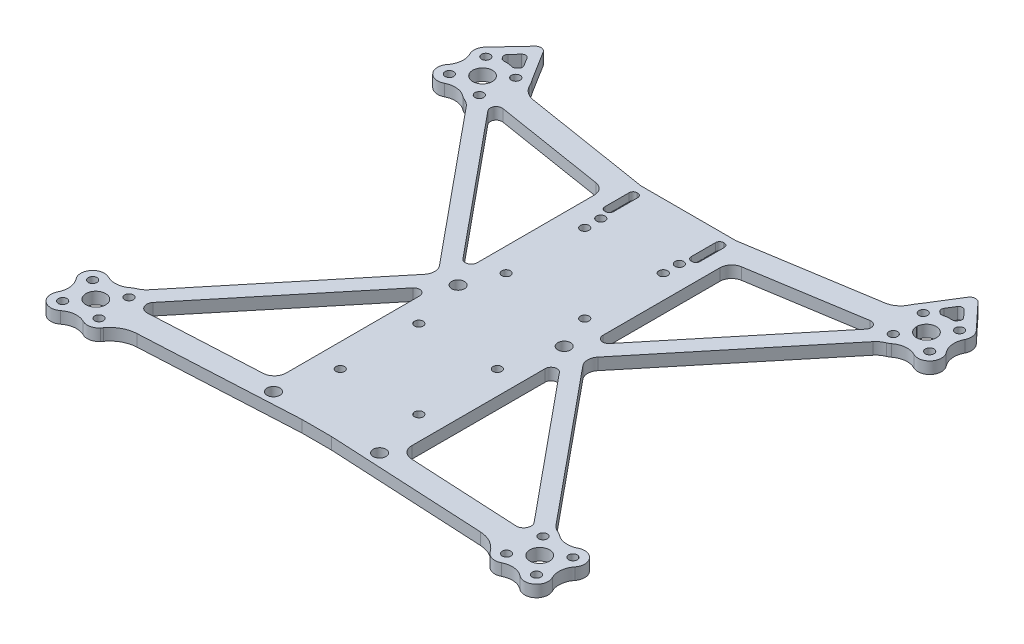
SolidWorks part; units mm, degrees
ref_plane "Front Plane" through (0, 0, 0) normal (0, 0, 1) x (1, 0, 0)
ref_plane "Top Plane" through (0, 0, 0) normal (0, 1, 0) x (1, 0, 0)
ref_plane "Right Plane" through (0, 0, 0) normal (1, 0, 0) x (0, 0, -1)
sketch "Sketch1" plane through (0, 0, 0) normal (0, 1, 0) x (1, 0, 0)
  line L0 (0, 42.225) -> (0, -42.225) construction
  line L1 (16, 42.225) -> (-16, 42.225)
  line L2 (16, 42.225) -> (16, -42.225)
  line L3 (16, -42.225) -> (-16, -42.225)
  line L4 (-16, 42.225) -> (-16, -42.225)
  line L5 (16, 42.225) -> (-16, -42.225) construction
  line L6 (16, -42.225) -> (-16, 42.225) construction
  line L12 (-12.1, 50.425) -> (-12.1, 52.425) construction
  line L13 (-7.9, 52.425) -> (7.9, 52.425)
  line L17 (-11, 52.425) -> (-11, 42.225) construction
  line L18 (-7.9, 42.225) -> (-14.1, 42.225)
  line L20 (-10, 36) -> (10, 36)
  line L21 (-10, 36) -> (-10, 16)
  line L22 (-10, 16) -> (10, 16)
  line L23 (10, 36) -> (10, 16)
  line L24 (-10, 36) -> (10, 16) construction
  line L25 (-10, 16) -> (10, 36) construction
  line L26 (-14.5, 10.775) -> (14.5, 10.775)
  line L27 (-14.5, 10.775) -> (-14.5, 41.225)
  line L28 (-14.5, 41.225) -> (14.5, 41.225)
  line L29 (14.5, 10.775) -> (14.5, 41.225)
  line L30 (-14.5, 10.775) -> (14.5, 41.225) construction
  line L31 (-14.5, 41.225) -> (14.5, 10.775) construction
  line L32 (-10, -6.225) -> (10, -6.225)
  line L33 (-10, -6.225) -> (-10, -26.225)
  line L34 (-10, -26.225) -> (10, -26.225)
  line L35 (10, -6.225) -> (10, -26.225)
  line L36 (-10, -6.225) -> (10, -26.225) construction
  line L37 (-10, -26.225) -> (10, -6.225) construction
  line L38 (-15.75, -36.225) -> (15.75, -36.225)
  line L39 (-15.75, -36.225) -> (-15.75, 3.775)
  line L40 (-15.75, 3.775) -> (15.75, 3.775)
  line L41 (15.75, -36.225) -> (15.75, 3.775)
  line L42 (-15.75, -36.225) -> (15.75, 3.775) construction
  line L43 (-15.75, 3.775) -> (15.75, -36.225) construction
  line L48 (-7.9, 42.225) -> (-7.9, 52.425)
  line L49 (-7.9, 52.425) -> (-14.1, 52.425)
  line L59 (-14.1, 42.225) -> (-14.1, 52.425)
  line L63 (-12.1, 50.425) -> (-9.9, 50.425)
  line L64 (-12.1, 50.425) -> (-12.1, 42.225)
  line L65 (-12.1, 42.225) -> (-9.9, 42.225)
  line L66 (-9.9, 50.425) -> (-9.9, 42.225)
  line L67 (-12.1, 50.425) -> (-9.9, 42.225) construction
  line L68 (-12.1, 42.225) -> (-9.9, 50.425) construction
  line L69 (-12.1, 50.425) -> (-14.1, 50.425) construction
  line L74 (7.9, 42.225) -> (14.1, 42.225)
  line L75 (14.1, 42.225) -> (14.1, 52.425)
  line L76 (7.9, 52.425) -> (14.1, 52.425)
  line L77 (7.9, 42.225) -> (7.9, 52.425)
  line L78 (12.1, 50.425) -> (9.9, 50.425)
  line L79 (12.1, 50.425) -> (12.1, 42.225)
  line L80 (12.1, 42.225) -> (9.9, 42.225)
  line L81 (9.9, 50.425) -> (9.9, 42.225)
  line L82 (-14.5, 10.775) -> (-14.5, 3.775) construction
  line L83 (-14.5, 7.275) -> (16, 7.275) construction
  line L89 (-13.5, -37.225) -> (-16, -37.225) construction
  line L94 (-14.1, 52.425) -> (-16, 52.425)
  line L95 (-14.1, 52.425) -> (-14.1, 42.225)
  line L96 (-14.1, 42.225) -> (-16, 42.225)
  line L97 (-16, 52.425) -> (-16, 42.225)
  line L98 (14.1, 52.425) -> (16, 52.425)
  line L99 (14.1, 52.425) -> (14.1, 42.225)
  line L100 (14.1, 42.225) -> (16, 42.225)
  line L101 (16, 52.425) -> (16, 42.225)
  circle A3 centre (-10, 36) radius 1.1
  circle A4 centre (10, 36) radius 1.1
  circle A5 centre (10, 16) radius 1.1
  circle A6 centre (-10, 16) radius 1.1
  circle A7 centre (-10, -6.225) radius 1.1
  circle A8 centre (10, -6.225) radius 1.1
  circle A9 centre (10, -26.225) radius 1.1
  circle A10 centre (-10, -26.225) radius 1.1
  circle A37 centre (-13.5, 7.275) radius 2.5
  circle A38 centre (-13.5, 7.275) radius 1.625
  circle A39 centre (13.5, 7.275) radius 1.625
  circle A40 centre (-13.5, -39.725) radius 2.5
  circle A41 centre (-13.5, -39.725) radius 1.625
  circle A42 centre (13.5, -39.725) radius 1.625
  circle A43 centre (-11, 46.325) radius 1.1
  circle A44 centre (11, 46.325) radius 1.1
  point P0 (0, 0)
  point P8 (0, 0)
  point P16 (0, 26)
  point P26 (0, 26)
  point P31 (0, -16.225)
  point P36 (0, -16.225)
  point P61 (-11, 46.325)
  dimension "D3" = 2
  dimension "D17" = 2.2
  dimension "D22" = 5
  dimension "D23" = 3.25
  dimension "D8" = 32
  dimension "D9" = 22
  dimension "D10" = 20
  dimension "D11" = 29
  dimension "D12" = 30.45
  dimension "D13" = 40
  dimension "D14" = 31.5
  dimension "D15" = 1
  dimension "D16" = 7
  dimension "D18" = 2.2
  dimension "D20" = 8.2
  dimension "D24" = 1
extrude "Base shape" add sketch "Sketch1" along normal blind 2 contours L63 L66 L1 L48 L49 L59 L18 L64 | L81 L78 L79 L1 L75 L76 L77 | L94 L97 L1 L59 | L101 L98 L75 L1 | L1 L77 L13 L48 | A43 L66 L63 L64 | A43 L64 L18 L66 | L79 A44 L81 L74 | L81 A44 L79 L78 | L1 L4 L3 L2 | A4 | A3 | A7 | A8 | A9 | A10 | A5 | A6 | A39 | A38 | A41 | A42 region at (15.05, 0, -47.325) region at (13.1, 0, -42.3444) region at (11, 0, -43.8523) region at (11, 0, -48.7977) region at (0, 0, -47.325) region at (-8.0194, 0, -47.325) region at (-15.05, 0, -47.325) region at (-11, 0, -43.8523) region at (-11, 0, -48.7977)
sketch "Sketch2" plane through (0, 2, 0) normal (0, -1, 0) x (1, 0, 0)
  line L0 (0, -52.425) -> (0, 42.225) construction
  line L1 (11.1, -42.225) -> (10.9, -42.225)
  line L2 (12.1, -43.225) -> (12.1, -49.425)
  line L3 (11.1, -50.425) -> (10.9, -50.425)
  line L4 (9.9, -43.225) -> (9.9, -49.425)
  line L5 (12.1, -42.225) -> (9.9, -50.425) construction
  line L6 (12.1, -50.425) -> (9.9, -42.225) construction
  line L7 (16, -52.425) -> (-16, -52.425) construction
  line L12 (16, 42.225) -> (-16, 42.225) construction
  line L13 (-11.1, -42.225) -> (-10.9, -42.225)
  line L14 (-12.1, -43.225) -> (-12.1, -49.425)
  line L15 (-11.1, -50.425) -> (-10.9, -50.425)
  line L20 (-9.9, -43.225) -> (-9.9, -49.425)
  arc A2 (12.1, -49.425) -> (11.1, -50.425) centre (11.1, -49.425) cw
  arc A3 (10.9, -50.425) -> (9.9, -49.425) centre (10.9, -49.425) cw
  arc A4 (10.9, -42.225) -> (9.9, -43.225) centre (10.9, -43.225) ccw
  arc A5 (11.1, -42.225) -> (12.1, -43.225) centre (11.1, -43.225) cw
  arc A6 (-10.9, -42.225) -> (-9.9, -43.225) centre (-10.9, -43.225) cw
  arc A7 (-11.1, -42.225) -> (-12.1, -43.225) centre (-11.1, -43.225) ccw
  arc A8 (-12.1, -49.425) -> (-11.1, -50.425) centre (-11.1, -49.425) ccw
  arc A9 (-10.9, -50.425) -> (-9.9, -49.425) centre (-10.9, -49.425) ccw
  point P0 (11, -46.325)
  dimension "D3" = 1
  dimension "D1" = 8.2
  dimension "D2" = 2.2
extrude "Cut-Extrude2" cut sketch "Sketch2" along normal blind 1
fillet "Main fillets" radius 2.5 4 edges at (-16, 1, -52.425) (16, 1, -52.425) (-16, 1, 42.225) (16, 1, 42.225)
sketch "Sketch3" plane through (0, 2, 0) normal (0, 1, 0) x (1, 0, 0)
  line L0 (-11.1, 50.425) -> (-10.9, 50.425) construction
  line L1 (-9.9, 49.425) -> (-9.9, 43.225) construction
  line L2 (-10.9, 42.225) -> (-11.1, 42.225) construction
  line L3 (-12.1, 43.225) -> (-12.1, 49.425) construction
  line L4 (-11.1, 50.425) -> (-10.9, 50.425)
  line L5 (-9.9, 49.425) -> (-9.9, 43.225)
  line L6 (-10.9, 42.225) -> (-11.1, 42.225)
  line L7 (-12.1, 43.225) -> (-12.1, 49.425)
  line L8 (13.5, 52.425) -> (-13.5, 52.425)
  line L9 (-16, 49.925) -> (-16, -39.725)
  line L10 (-13.5, -42.225) -> (13.5, -42.225)
  line L11 (16, -39.725) -> (16, 49.925)
  line L12 (10.9, 50.425) -> (11.1, 50.425) construction
  line L13 (12.1, 49.425) -> (12.1, 43.225) construction
  line L14 (11.1, 42.225) -> (10.9, 42.225) construction
  line L15 (9.9, 43.225) -> (9.9, 49.425) construction
  line L16 (13.5, 52.425) -> (-13.5, 52.425)
  line L17 (-16, 49.925) -> (-16, -39.725)
  line L18 (-13.5, -42.225) -> (13.5, -42.225)
  line L19 (16, -39.725) -> (16, 49.925)
  line L24 (10.9, 50.425) -> (11.1, 50.425)
  line L25 (12.1, 49.425) -> (12.1, 43.225)
  line L30 (11.1, 42.225) -> (10.9, 42.225)
  line L31 (9.9, 43.225) -> (9.9, 49.425)
  circle A0 centre (13.5, -39.725) radius 1.625 construction
  circle A1 centre (-13.5, -39.725) radius 1.625 construction
  circle A2 centre (-13.5, 7.275) radius 1.625 construction
  circle A3 centre (-10, -6.225) radius 1.1 construction
  circle A4 centre (-10, -26.225) radius 1.1 construction
  circle A5 centre (10, -26.225) radius 1.1 construction
  circle A6 centre (10, -6.225) radius 1.1 construction
  circle A7 centre (13.5, 7.275) radius 1.625 construction
  arc A8 (-13.5, 52.425) -> (-16, 49.925) centre (-13.5, 49.925) ccw
  arc A9 (-16, -39.725) -> (-13.5, -42.225) centre (-13.5, -39.725) ccw
  arc A10 (13.5, -42.225) -> (16, -39.725) centre (13.5, -39.725) ccw
  arc A11 (16, 49.925) -> (13.5, 52.425) centre (13.5, 49.925) ccw
  arc A13 (-11.1, 50.425) -> (-12.1, 49.425) centre (-11.1, 49.425) ccw construction
  arc A14 (-9.9, 49.425) -> (-10.9, 50.425) centre (-10.9, 49.425) ccw construction
  arc A16 (-13.5, 52.425) -> (-16, 49.925) centre (-13.5, 49.925) ccw
  arc A17 (-16, -39.725) -> (-13.5, -42.225) centre (-13.5, -39.725) ccw
  arc A18 (13.5, -42.225) -> (16, -39.725) centre (13.5, -39.725) ccw
  arc A19 (16, 49.925) -> (13.5, 52.425) centre (13.5, 49.925) ccw
  circle A24 centre (-10, 16) radius 1.1 construction
  circle A25 centre (-10, 36) radius 1.1 construction
  circle A26 centre (10, 36) radius 1.1 construction
  circle A27 centre (10, 16) radius 1.1 construction
  circle A28 centre (10, 16) radius 1.1
  circle A29 centre (10, 36) radius 1.1
  circle A30 centre (-10, 36) radius 1.1
  circle A31 centre (-10, 16) radius 1.1
  circle A32 centre (13.5, 7.275) radius 1.625
  circle A33 centre (10, -6.225) radius 1.1
  circle A34 centre (10, -26.225) radius 1.1
  circle A35 centre (-10, -26.225) radius 1.1
  circle A36 centre (-10, -6.225) radius 1.1
  circle A37 centre (13.5, -39.725) radius 1.625
  circle A38 centre (-13.5, -39.725) radius 1.625
  circle A39 centre (-13.5, 7.275) radius 1.625
  arc A40 (-10.9, 42.225) -> (-9.9, 43.225) centre (-10.9, 43.225) ccw construction
  arc A41 (-12.1, 43.225) -> (-11.1, 42.225) centre (-11.1, 43.225) ccw construction
  arc A42 (-11.1, 50.425) -> (-12.1, 49.425) centre (-11.1, 49.425) ccw
  arc A43 (-9.9, 49.425) -> (-10.9, 50.425) centre (-10.9, 49.425) ccw
  arc A44 (-10.9, 42.225) -> (-9.9, 43.225) centre (-10.9, 43.225) ccw
  arc A45 (-12.1, 43.225) -> (-11.1, 42.225) centre (-11.1, 43.225) ccw
  arc A46 (10.9, 50.425) -> (9.9, 49.425) centre (10.9, 49.425) ccw construction
  arc A47 (12.1, 49.425) -> (11.1, 50.425) centre (11.1, 49.425) ccw construction
  arc A48 (11.1, 42.225) -> (12.1, 43.225) centre (11.1, 43.225) ccw construction
  arc A49 (9.9, 43.225) -> (10.9, 42.225) centre (10.9, 43.225) ccw construction
  arc A50 (10.9, 50.425) -> (9.9, 49.425) centre (10.9, 49.425) ccw
  arc A51 (12.1, 49.425) -> (11.1, 50.425) centre (11.1, 49.425) ccw
  arc A52 (11.1, 42.225) -> (12.1, 43.225) centre (11.1, 43.225) ccw
  arc A53 (9.9, 43.225) -> (10.9, 42.225) centre (10.9, 43.225) ccw
  dimension "D1" = 0
extrude "Thicker base" add sketch "Sketch3" along normal blind 1
sketch "Sketch4" plane through (0, 0, 0) normal (0, -1, 0) x (1, 0, 0)
  line L0 (0, 13.9568) -> (0, -8.6953) construction
  line L1 (-13.1, -38.5) -> (-6.9, -38.5)
  line L2 (-14.1, -39.5) -> (-14.1, -40.7)
  line L3 (-13.1, -41.7) -> (-6.9, -41.7)
  line L4 (-5.9, -39.5) -> (-5.9, -40.7)
  line L5 (-10, -38.5) -> (-10, -41.7) construction
  line L7 (13.1, -38.5) -> (6.9, -38.5)
  line L8 (14.1, -39.5) -> (14.1, -40.7)
  line L9 (13.1, -41.7) -> (6.9, -41.7)
  line L10 (5.9, -39.5) -> (5.9, -40.7)
  line L12 (-14.1, -40.1) -> (-5.9, -40.1) construction
  circle A0 centre (-10, -36) radius 2
  arc A9 (14.1, -40.7) -> (13.1, -41.7) centre (13.1, -40.7) cw
  arc A10 (13.1, -38.5) -> (14.1, -39.5) centre (13.1, -39.5) cw
  arc A11 (6.9, -41.7) -> (5.9, -40.7) centre (6.9, -40.7) cw
  arc A12 (6.9, -38.5) -> (5.9, -39.5) centre (6.9, -39.5) ccw
  arc A13 (-6.9, -41.7) -> (-5.9, -40.7) centre (-6.9, -40.7) ccw
  arc A14 (-6.9, -38.5) -> (-5.9, -39.5) centre (-6.9, -39.5) cw
  arc A15 (-14.1, -40.7) -> (-13.1, -41.7) centre (-13.1, -40.7) ccw
  arc A16 (-13.1, -38.5) -> (-14.1, -39.5) centre (-13.1, -39.5) ccw
  point P9 (-10, -38)
  point P19 (14.1, -41.7)
  point P24 (14.1, -38.5)
  point P27 (5.9, -41.7)
  point P30 (5.9, -38.5)
  point P33 (-5.9, -41.7)
  point P36 (-5.9, -38.5)
  point P39 (-14.1, -41.7)
  point P42 (-14.1, -38.5)
  dimension "D5" = 4
  dimension "D6" = 1
  dimension "D1" = 8.2
  dimension "D2" = 3.2
  dimension "D3" = 10
  dimension "D4" = 0.5
extrude "Battery holder pockets" cut sketch "Sketch4" against normal blind 1 contours L4 L1 L2 L3 | L7 L10 L9 L8 region at (-10, 0, -40.1) region at (10, 0, -40.1)
sketch "Sketch5" plane through (0, 1, 0) normal (0, -1, 0) x (1, 0, 0)
  line L0 (-10, -38.5) -> (-10, -41.7) construction
  line L2 (-13.1, -41.7) -> (-6.9, -41.7) construction
  line L3 (0, 5.9884) -> (0, -5.6723) construction
  line L4 (-13.1, -38.5) -> (-6.9, -38.5) construction
  circle A0 centre (-10, -40.1) radius 1.1
  circle A1 centre (10, -40.1) radius 1.1
  dimension "D1" = 2.2
extrude "Battery holder holes" cut sketch "Sketch5" against normal up to next
sketch "Sketch6" [suppressed] plane through (0, 0, 0) normal (0, -1, 0) x (1, 0, 0)
  line L0 (0, -5.1) -> (0, 9.653) construction
  line L8 (-13.5, -7.275) -> (13.5, -7.275) construction
  line L10 (-16, -25.775) -> (16, -25.775) construction
  line L11 (-16, -49.925) -> (-16, 39.725) construction
  line L12 (16, -49.925) -> (16, 39.725) construction
  line L13 (17.5, -34.275) -> (19, -34.275)
  line L14 (16, -37.275) -> (19, -37.275)
  line L15 (16, -37.275) -> (16, -14.275)
  line L16 (16, -14.275) -> (19, -14.275)
  line L17 (19, -37.275) -> (19, -14.275)
  line L18 (16, -37.275) -> (19, -14.275) construction
  line L19 (16, -14.275) -> (19, -37.275) construction
  line L20 (16, -35.775) -> (17.5, -35.775)
  line L21 (16, -35.775) -> (16, -15.775)
  line L22 (16, -15.775) -> (17.5, -15.775)
  line L23 (17.5, -35.775) -> (17.5, -15.775)
  line L24 (16, -35.775) -> (17.5, -15.775) construction
  line L25 (16, -15.775) -> (17.5, -35.775) construction
  line L26 (17.5, -17.275) -> (19, -17.275)
  line L27 (-17.5, -34.275) -> (-19, -34.275)
  line L28 (-17.5, -17.275) -> (-19, -17.275)
  line L29 (-16, -35.775) -> (-16, -15.775)
  line L30 (-16, -35.775) -> (-17.5, -35.775)
  line L31 (-17.5, -35.775) -> (-17.5, -15.775)
  line L32 (-16, -15.775) -> (-17.5, -15.775)
  line L33 (-16, -37.275) -> (-16, -14.275)
  line L34 (-16, -37.275) -> (-19, -37.275)
  line L35 (-19, -37.275) -> (-19, -14.275)
  line L36 (-16, -14.275) -> (-19, -14.275)
  line L37 (16, 22.725) -> (19, 22.725)
  line L38 (16, 22.725) -> (16, -0.275)
  line L39 (16, -0.275) -> (19, -0.275)
  line L40 (19, 22.725) -> (19, -0.275)
  line L41 (16, 21.225) -> (17.5, 21.225)
  line L42 (16, 21.225) -> (16, 1.225)
  line L43 (16, 1.225) -> (17.5, 1.225)
  line L44 (17.5, 21.225) -> (17.5, 1.225)
  line L45 (17.5, 2.725) -> (19, 2.725)
  line L46 (17.5, 19.725) -> (19, 19.725)
  line L47 (-17.5, 19.725) -> (-19, 19.725)
  line L48 (-17.5, 2.725) -> (-19, 2.725)
  line L49 (-16, 21.225) -> (-16, 1.225)
  line L50 (-16, 21.225) -> (-17.5, 21.225)
  line L51 (-17.5, 21.225) -> (-17.5, 1.225)
  line L52 (-16, 1.225) -> (-17.5, 1.225)
  line L53 (-16, 22.725) -> (-16, -0.275)
  line L54 (-16, 22.725) -> (-19, 22.725)
  line L55 (-19, 22.725) -> (-19, -0.275)
  line L56 (-16, -0.275) -> (-19, -0.275)
  point P19 (17.5, -25.775)
  point P25 (16.75, -25.775)
  line M18 (16, -49.925) -> (16, 39.725)
  line M22 (-16, 39.725) -> (-16, -49.925)
  dimension "D1" = 14
  dimension "D4" = 23
  dimension "D5" = 3
  dimension "D6" = 1.5
  dimension "D7" = 20
  dimension "D8" = 1.5
extrude "Strap holders" [suppressed] add sketch "Sketch6" against normal up to surface (2 mm away) contours L23 L20 L14 L17 L13 M18 | L23 L26 L17 L16 L22 M18 | L45 L44 L43 L39 L40 M18 | L44 L46 L40 L37 L38 L41 | L54 L55 L47 L51 L50 M22 | L56 L52 L51 L48 L55 M22 | L36 L35 L28 L31 L32 M22 | L35 L34 L30 L31 L27 M22 up to face at (-10, 3, -39)
fillet "Strap holder fillets" [suppressed] radius 0.75
sketch "Sketch7" plane through (0, 3, 0) normal (0, 1, 0) x (1, 0, 0)
  line L0 (-56.5, 56.5) -> (-16, 50.0116) construction
  line L1 (56.5, -56.5) -> (-56.5, -56.5)
  line L2 (56.5, -56.5) -> (56.5, 56.5)
  line L3 (56.5, 56.5) -> (-56.5, 56.5)
  line L4 (-56.5, -56.5) -> (-56.5, 56.5)
  line L5 (56.5, -56.5) -> (-56.5, 56.5) construction
  line L6 (56.5, 56.5) -> (-56.5, -56.5) construction
  line L7 (-16, 49.925) -> (-16, -39.725) construction
  line L8 (-56.9746, 53.5378) -> (-16.4746, 47.0493)
  line L9 (-47.647, 58.1199) -> (-12.1, 52.425)
  line L10 (-56.0254, 59.4622) -> (-15.5254, 52.9738) construction
  line L11 (-13.5, 7.275) -> (13.5, 7.275) construction
  line L12 (-63.45, 50.7819) -> (-49.55, 62.2181) construction
  line L13 (-56.5, 56.5) -> (-16, 7.275) construction
  line L14 (-58.0444, 55.2293) -> (-17.5444, 6.0043)
  line L15 (-54.9556, 57.7707) -> (-14.4556, 8.5457)
  line L16 (-17.5444, 6.0043) -> (-16, 4.1271)
  line L17 (-56.5, 56.5) -> (-60.3121, 61.1333) construction
  line L18 (-56.5, 65.5) -> (-56.5, 47.5) construction
  line L19 (-60.3121, 61.1333) -> (-51.8667, 60.3121) construction
  line L20 (-56.0894, 60.7227) -> (-55.3151, 68.6852) construction
  line L21 (-56.4116, 69.7087) -> (-62.3842, 63.31)
  line L22 (-54.0419, 69.4782) -> (-49.414, 62.0488)
  line L23 (-55.4603, 67.1922) -> (-58.7341, 63.6848)
  line L24 (-55.4603, 67.1922) -> (-52.9235, 63.1198)
  line L25 (-58.0444, -40.6793) -> (-17.5444, 8.5457)
  line L26 (-54.9556, -43.2207) -> (-14.4556, 6.0043)
  line L27 (-56.5, -41.95) -> (-13.5, -39.725) construction
  line L28 (-47.871, -44.5075) -> (-3.7595, -42.225)
  line L29 (-56.655, -38.954) -> (-16, -36.8503)
  line L30 (-56.345, -44.946) -> (-14.5762, -42.7847) construction
  line L31 (-56.5, -41.95) -> (-14.7312, -39.7887) construction
  line L32 (-13.5, -42.225) -> (13.5, -42.225) construction
  line L33 (-56.655, -38.954) -> (-14.8862, -36.7927) construction
  line L34 (-16.4746, 47.0493) -> (-16, 46.9733)
  line L35 (-12.1, 49.425) -> (-12.1, 52.425) construction
  line L36 (13.5, 52.425) -> (-13.5, 52.425) construction
  circle A0 centre (-56.5, 56.5) radius 38.1
  circle A1 centre (-56.5, 56.5) radius 9
  circle A2 centre (-56.5, 56.5) radius 6
  circle A3 centre (-51.8667, 60.3121) radius 1.1
  circle A4 centre (-61.1333, 52.6879) radius 1.1
  circle A5 centre (-60.3121, 61.1333) radius 1.1
  circle A6 centre (-52.6879, 51.8667) radius 1.1
  circle A7 centre (-60.3121, 61.1333) radius 3
  circle A8 centre (-51.8667, 60.3121) radius 3
  circle A9 centre (-61.1333, 52.6879) radius 3
  circle A10 centre (-52.6879, 51.8667) radius 3
  circle A12 centre (-56.5, 56.5) radius 2.5
  circle A13 centre (-55.3151, 68.6852) radius 1.5
  circle A14 centre (-67.313, 57.5515) radius 4.864
  circle A15 centre (-57.5515, 45.687) radius 4.864
  circle A16 centre (-43.9819, 62.4587) radius 4.864
  circle A17 centre (-55.5501, 44.5421) radius 4.864
  circle A18 centre (-46.9606, 50.4143) radius 1.5
  circle A20 centre (-56.5, -41.95) radius 6
  circle A21 centre (-52.6879, -37.3167) radius 1.1
  circle A22 centre (-61.1333, -38.1379) radius 1.1
  circle A23 centre (-60.3121, -46.5833) radius 1.1
  circle A24 centre (-51.8667, -45.7621) radius 1.1
  circle A25 centre (-51.8667, -45.7621) radius 3
  circle A26 centre (-52.6879, -37.3167) radius 3
  circle A27 centre (-56.5, -41.95) radius 2.5
  circle A28 centre (-60.3121, -46.5833) radius 3
  circle A29 centre (-67.313, -43.0015) radius 4.864
  circle A30 centre (-61.1333, -38.1379) radius 3
  circle A31 centre (-57.5515, -31.137) radius 4.864
  circle A32 centre (-55.5501, -29.9921) radius 4.864
  circle A34 centre (-56.5, -41.95) radius 9
  circle A35 centre (-55.4485, -52.763) radius 4.864
  circle A38 centre (-43.36, -51.5674) radius 7.2836
  circle A39 centre (-47.0369, -36.5665) radius 1.8873
  point P0 (0, 0)
  point P15 (0, 0)
  point P36 (-52.6879, 51.8667)
  point P54 (-55.4603, 67.1922)
  point P111 (-12.1, 49.425)
  line M22 (13.5, 52.425) -> (-13.5, 52.425)
  arc M23 (-13.5, 52.425) -> (-16, 49.925) centre (-13.5, 49.925) ccw
  line M24 (-16, 49.925) -> (-16, -39.725)
  arc M25 (-16, -39.725) -> (-13.5, -42.225) centre (-13.5, -39.725) ccw
  line M26 (-13.5, -42.225) -> (13.5, -42.225)
  dimension "D3" = 76.2
  dimension "D4" = 12
  dimension "D5" = 3
  dimension "D10" = 2.2
  dimension "D11" = 5
  dimension "D12" = 3
  dimension "D16" = 3
  dimension "D1" = 113
  dimension "D13" = 8
  dimension "D6" = 3
  dimension "D7" = 3
  dimension "D8" = 2
  dimension "D9" = 2
  dimension "D14" = 3
  dimension "D15" = 3
extrude "Arms" add sketch "Sketch7" against normal up to surface (3 mm away) contours A0 L8 L34 L9 M24 M23 M22 | A1 L8 A0 L9 L3 | A10 L8 A1 L3 A2 | A16 L3 L9 | A8 A2 L3 A1 | A2 A8 A3 | A2 A8 A3 | A12 L3 A2 A8 A7 A9 L4 L14 | A12 L15 A10 A2 L3 | A12 L4 L8 A10 L15 | A12 L14 L8 L4 | A10 L8 L4 L14 | A10 L14 L4 A2 | L8 L14 L4 | A14 A9 A2 | A14 A2 A7 | A15 A2 A9 | A15 A10 A2 L4 | A10 L15 A1 L8 | A10 A1 L15 | A17 A1 L14 A10 | A10 L14 A1 | A17 L14 A1 | A1 L14 A0 L15 | A8 A1 L24 | A13 L24 A1 L22 | A13 | A13 L21 A1 L23 | A7 L23 A1 | A0 L14 L16 L15 M24 | L25 A34 L26 L16 L14 | L29 A34 L28 M26 M25 M24 | A39 L26 A34 | A39 A34 L29 | A34 L25 A26 | A34 A32 A26 L25 | A32 A34 L25 | A26 A31 L4 A20 | L4 A31 A20 | L25 A26 A20 L4 | A20 A30 A28 L4 A27 L25 | A20 A31 A30 | A20 A30 A29 | A20 A29 A28 | A35 L4 A20 A28 | A35 A25 A20 | L26 A27 L4 A20 A25 A26 | A35 A20 L4 | L4 A27 L26 A26 L29 | L29 A26 L25 L4 | L25 L29 L4 | L25 A27 L4 L29 | A38 L28 A34 | A34 L29 A26 A20 A25 | A34 L26 A26 L29 | A34 A26 L26 | A15 L4 A2 | A18 L8 A1 L15 | A1 L3 L9 | A7 | A5 | A9 | A4 | A10 | A6 | A26 | A21 | A30 | A22 | A28 | A23 | A25 | A24 region at (-47.184, 3, 45.066) region at (-31.3338, 3, 40.711) region at (-32.8289, 3, -52.5874) region at (-44.211, 3, -57.0386) region at (-17.1717, 3, -50.3538) region at (-48.9969, 3, 41.7471) region at (-49.1236, 3, -54.6581) region at (-48.8324, 3, -58.0351) region at (-47.1282, 3, -58.5028) region at (-24.1765, 3, -17.1136) region at (-41.5668, 3, -38.3497) region at (-57.4052, 3, 48.163) region at (-54.4445, 3, 47.8724) region at (-51.8807, 3, -55.6768) region at (-52.205, 3, -56.6697) region at (-49.2822, 3, -51.8002) region at (-48.4949, 3, -51.2849) region at (-52.3363, 3, -48.2332) region at (-34.0657, 3, 14.6748) region at (-56.355, 3, 47.9664) region at (-62.4224, 3, 44.0055) region at (-57.252, 3, 47.2609) region at (-55.1154, 3, 47.6835) region at (-48.0098, 3, 38.2823) region at (-49.1686, 3, 37.7777) region at (-54.4837, 3, -54.6883) region at (-53.0659, 3, -59.3254) region at (-50.9193, 3, -61.0916) region at (-49.7951, 3, -50.7418) region at (-52.9788, 3, -65.9755) region at (-52.3363, 3, 33.6832) region at (-52.9015, 3, -48.7171) region at (-52.1414, 3, -48.8113) region at (-49.026, 3, 36.4293) region at (-55.3151, 3, -68.6852) region at (-52.4447, 3, -63.9477) region at (-52.1414, 3, 34.2613) region at (-52.9015, 3, 34.1671) region at (-58.5555, 3, 36.0276) region at (-58.5555, 3, -50.5776) region at (-62.7075, 3, 41.0741) region at (-49.7951, 3, 36.1918) region at (-56.6984, 3, -53.811) region at (-55.8748, 3, -53.0321) region at (-58.1296, 3, -66.4764) region at (-55.5948, 3, 35.737) region at (-56.645, 3, 35.9336) region at (-56.645, 3, -50.4836) region at (-55.5948, 3, -50.287) region at (-62.7075, 3, -55.6241) region at (-56.701, 3, 39.2669) region at (-54.4356, 3, 40.1886) region at (-56.5346, 3, -53.4308) region at (-56.0913, 3, -51.6584) region at (-59.0444, 3, -64.5895) region at (-56.0913, 3, 37.1084) region at (-62.4224, 3, -58.5555) region at (-56.5412, 3, 38.9002) region at (-55.8564, 3, 38.5438) up to face at (-13.5, 0, 41.35)
fillet "Motor protector fillets" radius 1 5 edges at (-52.9235, 1.5, -63.1198) (-54.2913, 1.5, -62.0787) (-57.5925, 1.5, -62.3997) (-58.7341, 1.5, -63.6848) (-55.4603, 1.5, -67.1922)
mirror "Arms mirror" about plane through (0, 0, 0) normal (1, 0, 0) of "Arms", "Motor protector fillets"
fillet "Arm fillets outer" radius 3 6 edges at (-16, 1.5, 36.8503) (-16, 1.5, -46.9733) (-18.5899, 1.5, -7.275) (16, 1.5, 36.8503) (18.5899, 1.5, -7.275) (16, 1.5, -46.9733)
fillet "Arm fillets inner" radius 1.5 4 edges at (-16, 1.5, -10.4229) (-16, 1.5, -4.1271) (16, 1.5, -4.1271) (16, 1.5, -10.4229)
